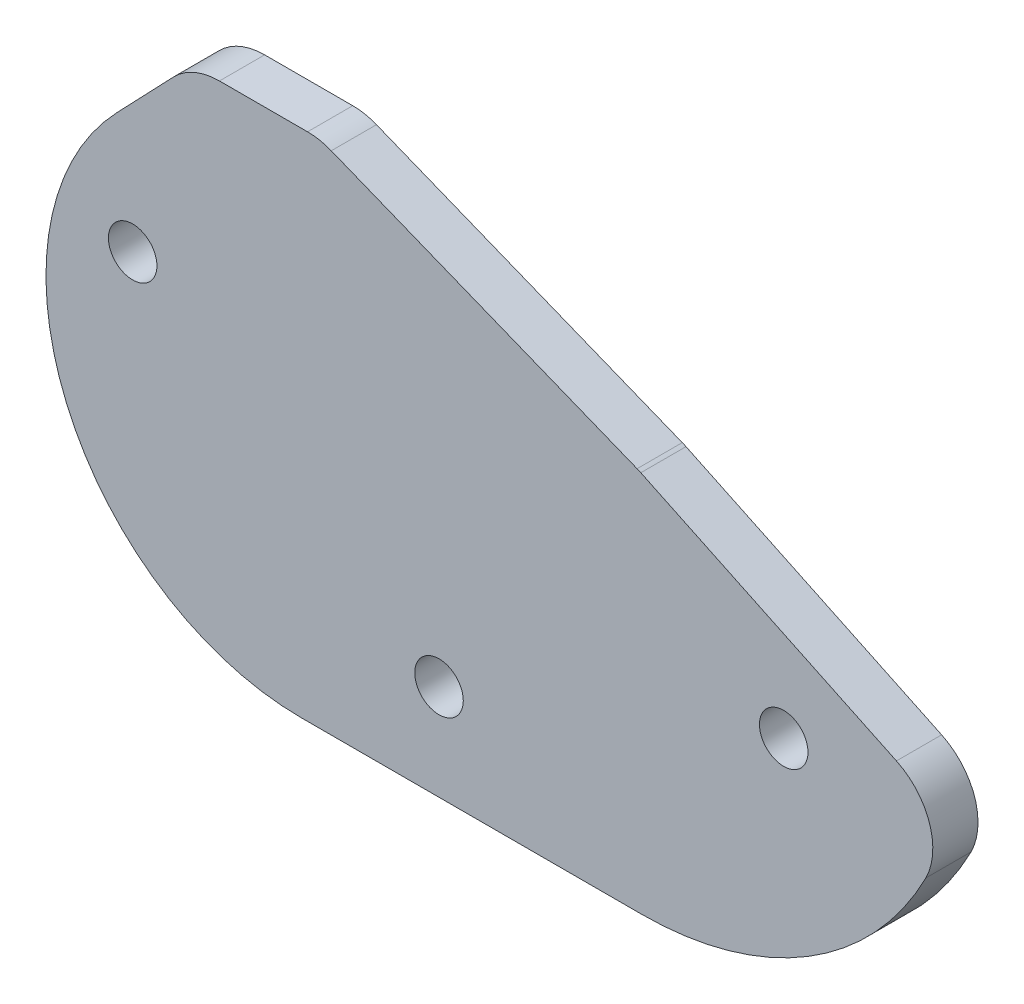
SolidWorks part; units mm, degrees
material "Titanium"
ref_plane "Front Plane" through (0, 0, 0) normal (0, 0, 1) x (1, 0, 0)
ref_plane "Top Plane" through (0, 0, 0) normal (0, 1, 0) x (1, 0, 0)
ref_plane "Right Plane" through (0, 0, 0) normal (1, 0, 0) x (0, 0, -1)
sketch "Sketch1" plane through (0, 0, 0) normal (0, 0, 1) x (1, 0, 0)
  line L0 (26.2421, 50.8) -> (0, 23.368)
  line L1 (26.2421, 50.8) -> (38.9421, 50.8)
  line L2 (38.9421, 50.8) -> (70.6921, 38.0905)
  line L3 (70.6921, 38.0905) -> (101.6, 23.368)
  line L4 (101.6, 23.368) -> (101.6, 0)
  line L5 (101.6, 0) -> (0, 0)
  line L6 (0, 23.368) -> (0, 0)
  circle A0 centre (20.32, 31.75) radius 2.413
  circle A1 centre (50.8, 9.525) radius 2.413
  circle A2 centre (85.09, 22.225) radius 2.413
  dimension "D8" = 4.826
  dimension "D1" = 12.7
  dimension "D2" = 23.368
  dimension "D3" = 25.47
  dimension "D4" = 31.75
  dimension "D5" = 46.27
  dimension "D6" = 50.8
  dimension "D7" = 101.6
  dimension "D9" = 9.525
  dimension "D10" = 30.48
  dimension "D11" = 34.29
  dimension "D12" = 12.7
  dimension "D13" = 50.8
  dimension "D14" = 22.225
extrude "Extrude1" add sketch "Sketch1" along normal blind 4.4958
sketch "Sketch2" plane through (0, 0, 4.4958) normal (0, 0, 1) x (1, 0, 0)
  line L0 (26.2421, 50.8) -> (0, 23.368) construction
  line L1 (0, 0) -> (101.6, 0) construction
  line L2 (18.7403, 42.958) -> (0, 23.368)
  line L3 (0, 23.368) -> (0, 0)
  line L4 (0, 0) -> (37.0944, 0)
  line L5 (101.6, 23.368) -> (101.6, 0)
  line L6 (101.6, 0) -> (70.9764, 0)
  arc A0 (18.7403, 42.958) -> (37.0944, 0) centre (37.0944, 25.4) ccw
  arc A1 (101.6, 23.368) -> (70.9764, 0) centre (70.9764, 31.75) cw
  dimension "D1" = 25.4
  dimension "D2" = 31.75
extrude "Cut-Extrude1" cut sketch "Sketch2" against normal through all
fillet "Fillet1" radius 6.35 4 edges at (26.2421, 50.8, 2.2479) (38.9421, 50.8, 2.2479) (70.6921, 38.0905, 2.2479) (101.6, 23.368, 2.2479)
